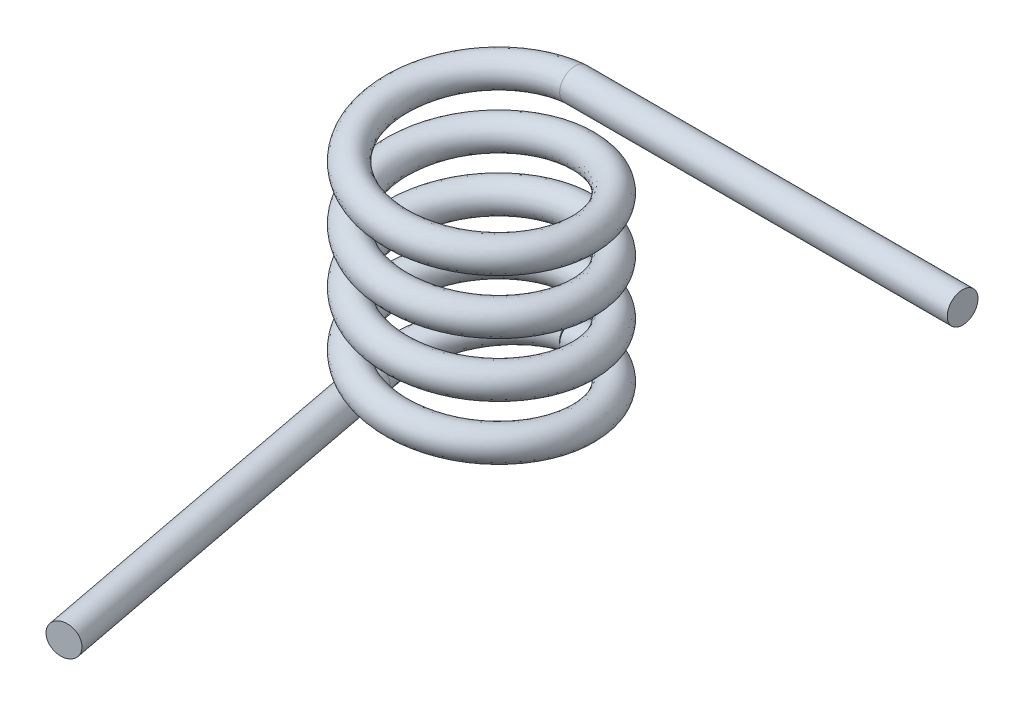
SolidWorks part; units mm, degrees
ref_plane "Front Plane" through (0, 0, 0) normal (0, 0, 1) x (1, 0, 0)
ref_plane "Top Plane" through (0, 0, 0) normal (0, 1, 0) x (1, 0, 0)
ref_plane "Right Plane" through (0, 0, 0) normal (1, 0, 0) x (0, 0, -1)
sketch "Sketch1" plane through (0, 0, 0) normal (0, 1, 0) x (1, 0, 0)
  circle A0 centre (0, 0) radius 2
  dimension "D1" = 4
curve "Helix/Spiral1" pitch 1.125 height 4.5 radius 2 left hand yes centre (0, 0, 0) axis (0, 1, 0) start towards (0, 0, -1)
sketch "Sketch2" plane through (0, 0, 0) normal (1, 0, 0) x (0, 0, -1)
  circle A0 centre (-1.9323, 0.5158) radius 0.3175
  spline S0 degree 3 poles (2, 0) (2, 0.0233) (1.8959, 0.0704) (1.451, 0.1406) (0.7853, 0.2109) (0, 0.2812) (-0.7853, 0.3516) (-1.451, 0.4219) (-1.8959, 0.4922) (-2.0521, 0.5625) (-1.8959, 0.6328) (-1.451, 0.7031) (-0.7853, 0.7734) (0, 0.8437) (0.7853, 0.9141) (1.451, 0.9844) (1.8959, 1.0547) (2.0521, 1.125) (1.8959, 1.1953) (1.451, 1.2656) (0.7853, 1.3359) (0, 1.4062) (-0.7853, 1.4766) (-1.451, 1.5469) (-1.8959, 1.6172) (-2.0521, 1.6875) (-1.8959, 1.7578) (-1.451, 1.8281) (-0.7853, 1.8984) (0, 1.9688) (0.7853, 2.0391) (1.451, 2.1094) (1.8959, 2.1797) (2.0521, 2.25) (1.8959, 2.3203) (1.451, 2.3906) (0.7853, 2.4609) (0, 2.5312) (-0.7853, 2.6016) (-1.451, 2.6719) (-1.8959, 2.7422) (-2.0521, 2.8125) (-1.8959, 2.8828) (-1.451, 2.9531) (-0.7853, 3.0234) (0, 3.0938) (0.7853, 3.1641) (1.451, 3.2344) (1.8959, 3.3047) (2.0521, 3.375) (1.8959, 3.4453) (1.451, 3.5156) (0.7853, 3.5859) (0, 3.6563) (-0.7853, 3.7266) (-1.451, 3.7969) (-1.8959, 3.8672) (-2.0521, 3.9375) (-1.8959, 4.0078) (-1.451, 4.0781) (-0.7853, 4.1484) (0, 4.2188) (0.7853, 4.2891) (1.451, 4.3594) (1.8959, 4.4296) (2, 4.4767) (2, 4.5) knots 0 0 0 0 0.015625 0.03125 0.046875 0.0625 0.078125 0.09375 0.109375 0.125 0.140625 0.15625 0.171875 0.1875 0.203125 0.21875 0.234375 0.25 0.265625 0.28125 0.296875 0.3125 0.328125 0.34375 0.359375 0.375 0.390625 0.40625 0.421875 0.4375 0.453125 0.46875 0.484375 0.5 0.515625 0.53125 0.546875 0.5625 0.578125 0.59375 0.609375 0.625 0.640625 0.65625 0.671875 0.6875 0.703125 0.71875 0.734375 0.75 0.765625 0.78125 0.796875 0.8125 0.828125 0.84375 0.859375 0.875 0.890625 0.90625 0.921875 0.9375 0.953125 0.96875 0.984375 1 1 1 1 construction
  dimension "D1" = 0.635
  dimension "D2" = 2
sweep "Sweep1" add profiles "Sketch2" path "Helix/Spiral1"
sketch "Sketch11" plane through (0, 0, 0) normal (0, 0, 1) x (1, 0, 0)
  line L0 (0, 4.4533) -> (3.1878, 4.7322)
  line L1 (0, 4.1358) -> (0, 4.7708) construction
  dimension "D1" = 85
sketch "Sketch3" plane through (0, 0, 0) normal (1, 0, 0) x (0, 0, -1)
  circle A0 centre (5, 17.5) radius 0.3175
extrude "Boss-Extrude1" [suppressed] add sketch "Sketch3" along direction (0.9962, 0.0872, 0) on the side of the normal blind 4
sketch "Sketch5" plane through (0, 0, 0) normal (-1, 0, 0) x (0, 0, 1)
  circle A0 centre (-1.93, 0) radius 0.3175
  dimension "D1" = 0.635
  dimension "D2" = 1.93
sketch "Sketch8" plane through (0, 0, 0) normal (0, 1, 0) x (1, 0, 0)
  circle A0 centre (0, 0) radius 2.25
  dimension "D1" = 4.5
curve "Helix/Spiral2" pitch 2.1875 height 0.6125 radius 2.25 left hand yes centre (0, 0, 0) axis (0, -1, 0) start towards (0, 0, -1)
sweep "Sweep3" add profiles "Sketch5" path "Helix/Spiral2"
sketch "Sketch12" plane through (0, 0, 0) normal (1, 0, 0) x (0, 0, -1)
  circle A0 centre (1.9323, 4.4533) radius 0.3175
extrude "Boss-Extrude4" add sketch "Sketch12" along normal blind 8
sketch "Sketch15" plane through (0, 0, 0) normal (0.1873, 0, 0.9823) x (0.9823, 0, -0.1873)
  circle A0 centre (-1.93, -0.6132) radius 0.3175
extrude "Boss-Extrude7" add sketch "Sketch15" along normal blind 8
